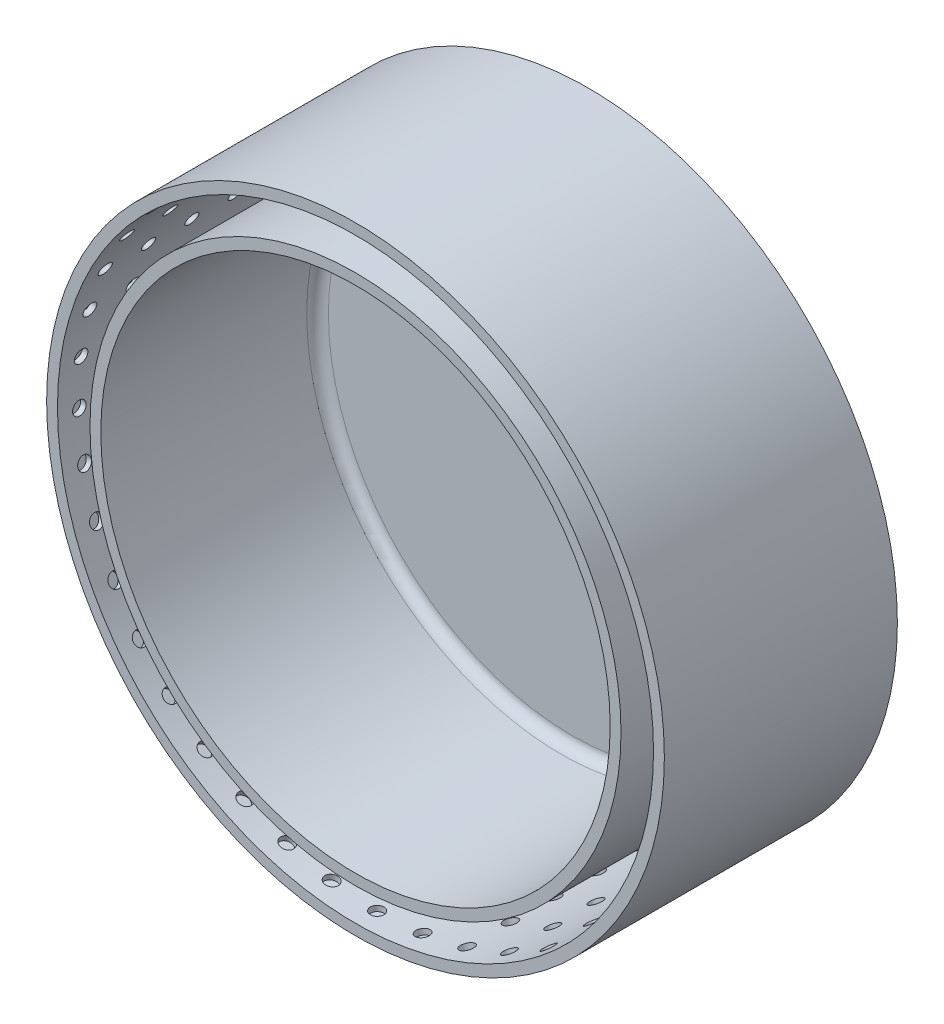
SolidWorks part; units mm, degrees
ref_plane "Front Plane" through (0, 0, 0) normal (0, 0, 1) x (1, 0, 0)
ref_plane "Top Plane" through (0, 0, 0) normal (0, 1, 0) x (1, 0, 0)
ref_plane "Right Plane" through (0, 0, 0) normal (1, 0, 0) x (0, 0, -1)
sketch "Sketch1" plane through (0, 0, 0) normal (0, 0, 1) x (1, 0, 0)
  circle A0 centre (0, 0) radius 55
  circle A1 centre (0, 0) radius 57
  dimension "D1" = 110
  dimension "D2" = 2
extrude "Boss-Extrude1" add sketch "Sketch1" along normal blind 40
sketch "Sketch2" plane through (0, 0, 0) normal (0, 0, -1) x (-1, 0, 0)
  circle A0 centre (0, 0) radius 57
  point P6 (0, 0)
  dimension "D1" = 114
extrude "Boss-Extrude2" add sketch "Sketch2" along normal blind 3
sketch "Sketch3" plane through (0, 0, 0) normal (0, 1, 0) x (1, 0, 0)
  line L0 (-57, -40) -> (57, -40) construction
  circle A0 centre (0, -36) radius 1.25
  dimension "D1" = 2.5
  dimension "D2" = 4
extrude "Cut-Extrude1" cut sketch "Sketch3" against normal blind 56
pattern_circular "CirPattern1" count 41 over 360 about axis through (0, 0, 0) along (0, 0, 1) of "Cut-Extrude1"
pattern_linear "LPattern3" count 5 spacing 8 along (0, 0, -1) of "CirPattern1", "Cut-Extrude1"
sketch "Sketch4" plane through (0, 0, 0) normal (0, 0, 1) x (1, 0, 0)
  circle A0 centre (0, 0) radius 49
  circle A1 centre (0, 0) radius 47
  dimension "D1" = 98
  dimension "D2" = 2
extrude "Boss-Extrude3" add sketch "Sketch4" along normal up to surface (40 mm away) up to face at (57, 0, 40)
fillet "Fillet1" radius 2 2 edges at (55, 0, 0) (47, 0, 0)
